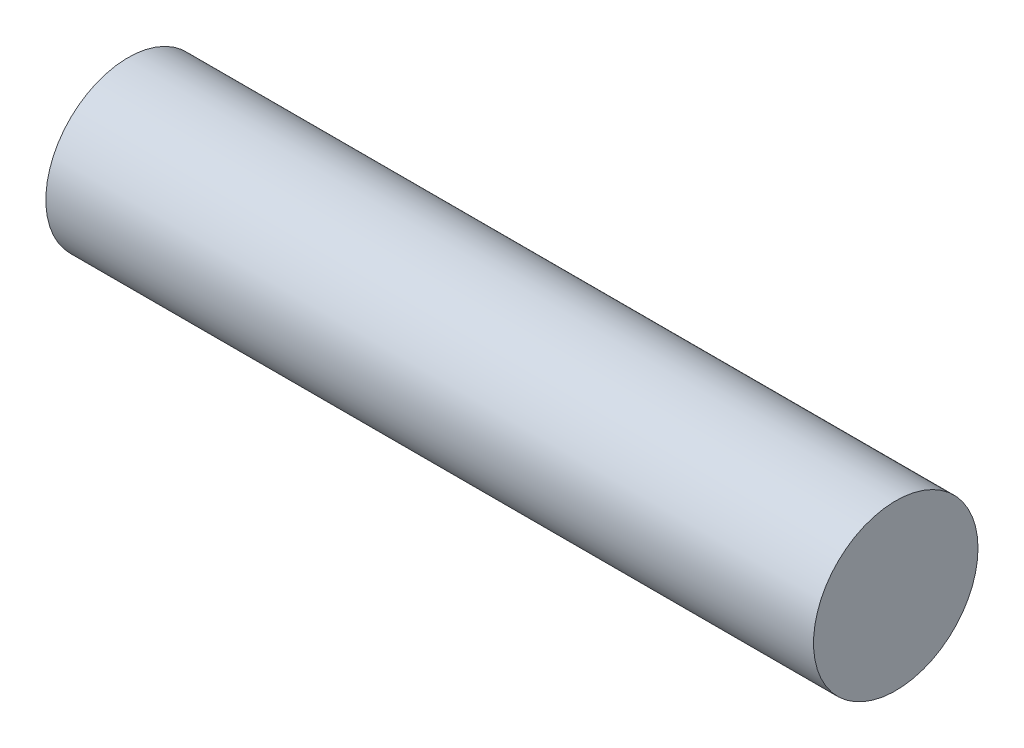
SolidWorks part; units mm, degrees
ref_plane "Front Plane" through (0, 0, 0) normal (0, 0, 1) x (1, 0, 0)
ref_plane "Top Plane" through (0, 0, 0) normal (0, 1, 0) x (1, 0, 0)
ref_plane "Right Plane" through (0, 0, 0) normal (1, 0, 0) x (0, 0, -1)
sketch "Sketch1" plane through (0, 0, 0) normal (1, 0, 0) x (0, 0, -1)
  circle A0 centre (0, 0) radius 9.525
  dimension "D1" = 19.05
extrude "Boss-Extrude1" add sketch "Sketch1" along normal blind 88.9
